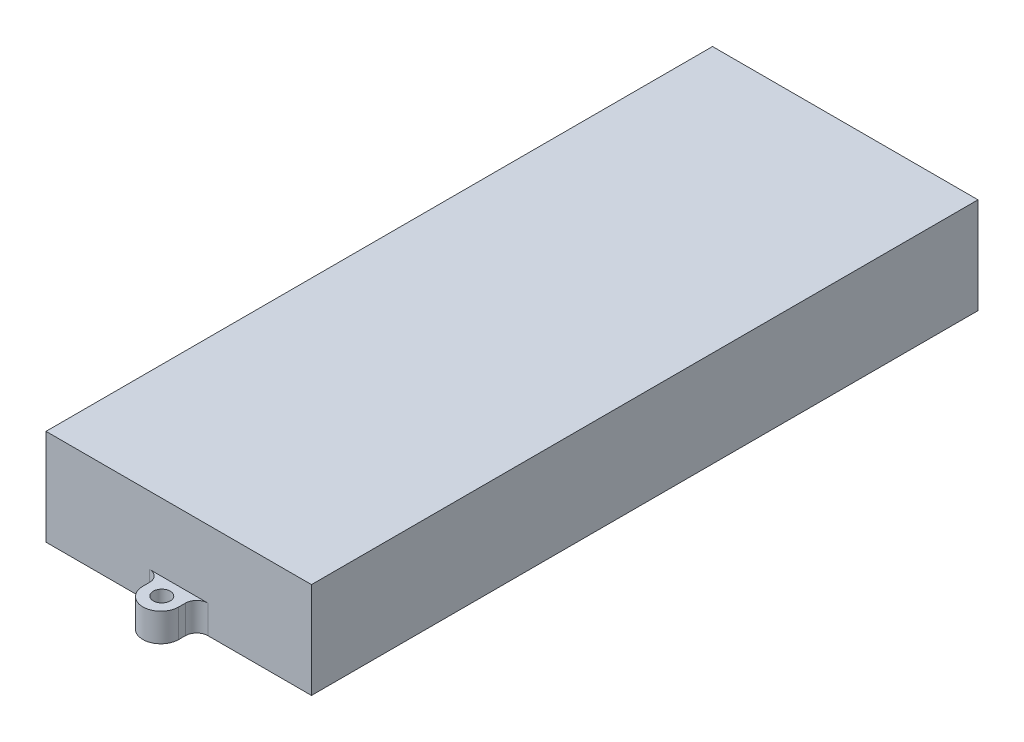
SolidWorks part; units mm, degrees
ref_plane "Front Plane" through (0, 0, 0) normal (0, 0, 1) x (1, 0, 0)
ref_plane "Top Plane" through (0, 0, 0) normal (0, 1, 0) x (1, 0, 0)
ref_plane "Right Plane" through (0, 0, 0) normal (1, 0, 0) x (0, 0, -1)
sketch "Sketch1" plane through (0, 0, 0) normal (0, 1, 0) x (1, 0, 0)
  line L1 (-23.5, -59) -> (23.5, -59)
  line L2 (-23.5, -59) -> (-23.5, 59)
  line L3 (-23.5, 59) -> (23.5, 59)
  line L4 (23.5, -59) -> (23.5, 59)
  line L5 (-23.5, -59) -> (23.5, 59) construction
  line L6 (-23.5, 59) -> (23.5, -59) construction
  point P0 (0, 0)
  dimension "D1" = 47
  dimension "D2" = 118
extrude "Boss-Extrude1" add sketch "Sketch1" along normal blind 17
sketch "Sketch2" plane through (0, 0, 0) normal (0, 1, 0) x (1, 0, 0)
  line L0 (-25.7921, 0) -> (26.5568, 0) construction
  line L1 (-3.175, 62.175) -> (-3.175, 59)
  line L6 (3.175, 62.175) -> (3.175, 59)
  line L7 (3.175, -62.175) -> (3.175, -59)
  line L9 (-3.175, -62.175) -> (-3.175, -59)
  line L10 (-3.175, 59) -> (3.175, 59)
  line L11 (-3.175, -59) -> (3.175, -59)
  arc A0 (3.175, 62.175) -> (-3.175, 62.175) centre (0, 62.175) ccw
  arc A1 (3.175, -62.175) -> (-3.175, -62.175) centre (0, -62.175) cw
  dimension "D1" = 6.35
  dimension "D2" = 59
extrude "Boss-Extrude2" add sketch "Sketch2" along normal blind 5
sketch "Sketch3" plane through (0, 5, 0) normal (0, 1, 0) x (1, 0, 0)
  line L0 (0, 0) -> (23.5, 0) construction
  line L1 (23.5, -59) -> (23.5, 59) construction
  line L2 (0, 65.35) -> (0, -65.35) construction
  circle A0 centre (0, -62) radius 1.5
  circle A1 centre (0, 62) radius 1.5
  arc A2 (3.175, 62.175) -> (-3.175, 62.175) centre (0, 62.175) ccw construction
  arc A3 (-3.175, -62.175) -> (3.175, -62.175) centre (0, -62.175) ccw construction
  point P11 (0, 0)
  point P12 (0, 0)
  dimension "D1" = 3
  dimension "D2" = 124
extrude "Cut-Extrude1" cut sketch "Sketch3" against normal through all
fillet "Fillet2" radius 2 4 edges at (3.175, 2.5, -59) (-3.175, 2.5, -59) (-3.175, 2.5, 59) (3.175, 2.5, 59)
